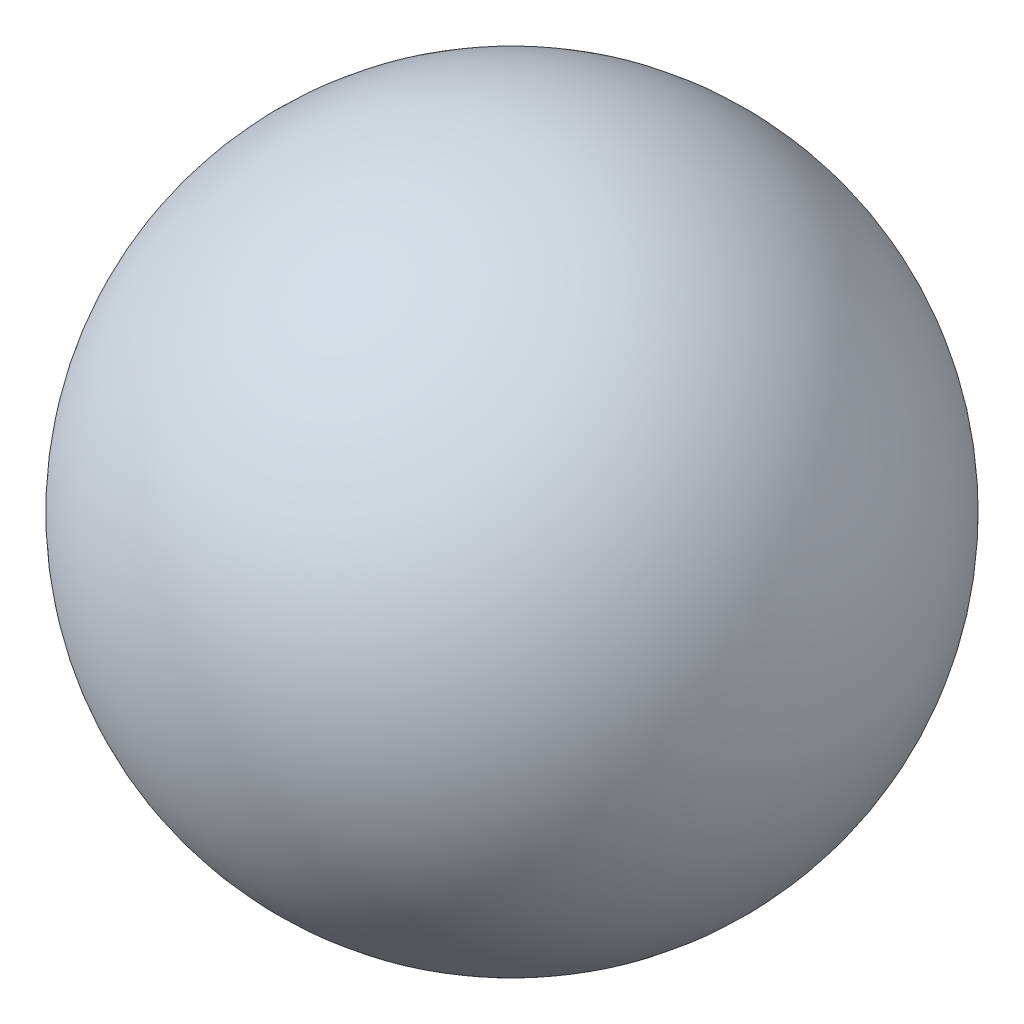
SolidWorks part; units mm, degrees
material "AISI Type 316L stainless steel"
ref_plane "Front Plane" through (0, 0, 0) normal (0, 0, 1) x (1, 0, 0)
ref_plane "Top Plane" through (0, 0, 0) normal (0, 1, 0) x (1, 0, 0)
ref_plane "Right Plane" through (0, 0, 0) normal (1, 0, 0) x (0, 0, -1)
sketch "Sketch1" plane through (0, 0, 0) normal (0, 0, 1) x (1, 0, 0)
  line L0 (0, 0) -> (0, 9.525)
  arc A1 (0, 0) -> (0, 9.525) centre (0, 4.7625) ccw
  dimension "D1" = 9.525
revolve "Revolve1" add sketch "Sketch1" angle 360 about L0
